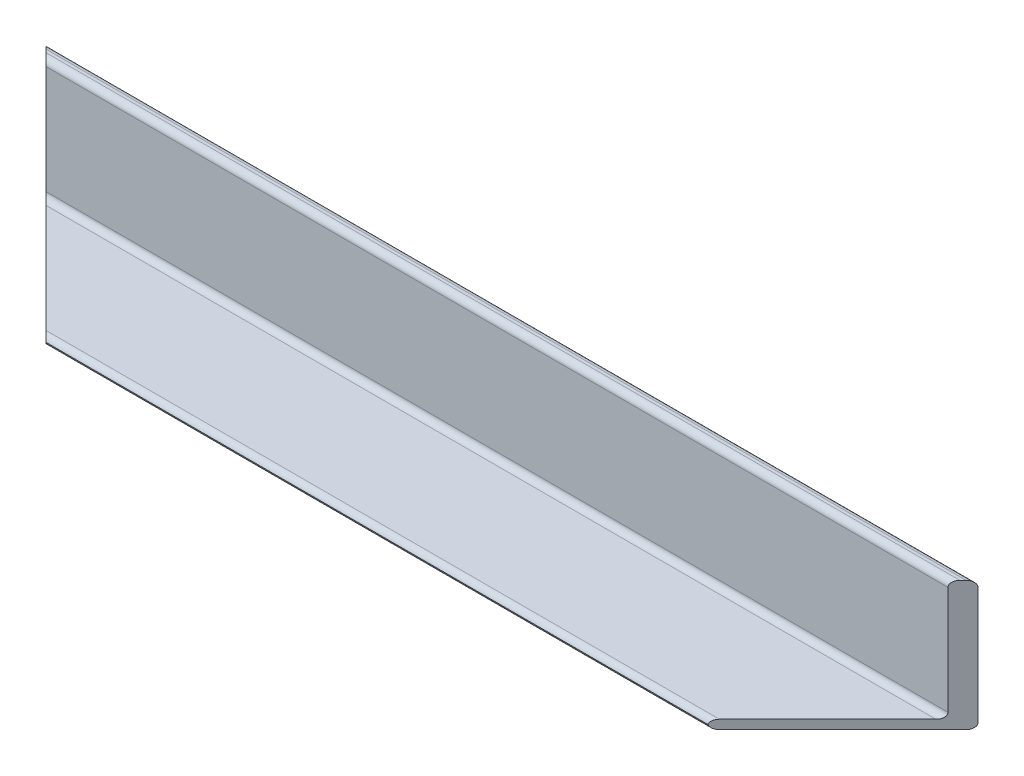
SolidWorks part; units mm, degrees
ref_plane "Front Plane" through (0, 0, 0) normal (0, 0, 1) x (1, 0, 0)
ref_plane "Top Plane" through (0, 0, 0) normal (0, 1, 0) x (1, 0, 0)
ref_plane "Right Plane" through (0, 0, 0) normal (1, 0, 0) x (0, 0, -1)
sketch "Sketch1" plane through (0, 0, 0) normal (0, 1, 0) x (1, 0, 0)
  line L1 (-77.5, 11.25) -> (77.5, 11.25)
  line L2 (-77.5, 11.25) -> (-77.5, -11.25)
  line L3 (-77.5, -11.25) -> (77.5, -11.25)
  line L4 (77.5, 11.25) -> (77.5, -11.25)
  line L5 (-77.5, 11.25) -> (77.5, -11.25) construction
  line L6 (-77.5, -11.25) -> (77.5, 11.25) construction
  point P0 (0, 0)
  dimension "D1" = 155
  dimension "D2" = 22.5
extrude "Boss-Extrude1" add sketch "Sketch1" along normal blind 1.5
sketch "Sketch2" plane through (0, 1.5, 0) normal (0, 1, 0) x (1, 0, 0)
  line L0 (77.5, -11.25) -> (77.5, 11.25) construction
  line L1 (-77.5, 11.25) -> (77.5, 11.25)
  line L2 (-77.5, 11.25) -> (-77.5, 8.75)
  line L3 (-77.5, 8.75) -> (77.5, 8.75)
  line L4 (77.5, 11.25) -> (77.5, 8.75)
  dimension "D1" = 2.5
extrude "Boss-Extrude2" add sketch "Sketch2" along normal blind 20
sketch "Sketch3" plane through (0, 0, 0) normal (0, -1, 0) x (-1, 0, 0)
  line L2 (-77.5, -11.25) -> (-55, -11.25)
  line L3 (-77.5, -11.25) -> (-77.5, 11.25)
  line L4 (77.5, -11.25) -> (77.5, 11.25)
  line L6 (77.5, -11.25) -> (55, -11.25)
  line L7 (77.5, -11.25) -> (-77.5, -11.25) construction
  line L8 (55, -11.25) -> (77.5, 11.25)
  line L9 (-55, -11.25) -> (-77.5, 11.25)
  dimension "D1" = 45
  dimension "D2" = 45
extrude "Cut-Extrude2" cut sketch "Sketch3" against normal through all
fillet "Fillet1" radius 1 6 edges at (0, 0, -11.25) (0, 21.5, -11.25) (0, 0, 11.25) (0, 1.5, 11.25) (0, 1.5, -8.75) (0, 21.5, -8.75)
